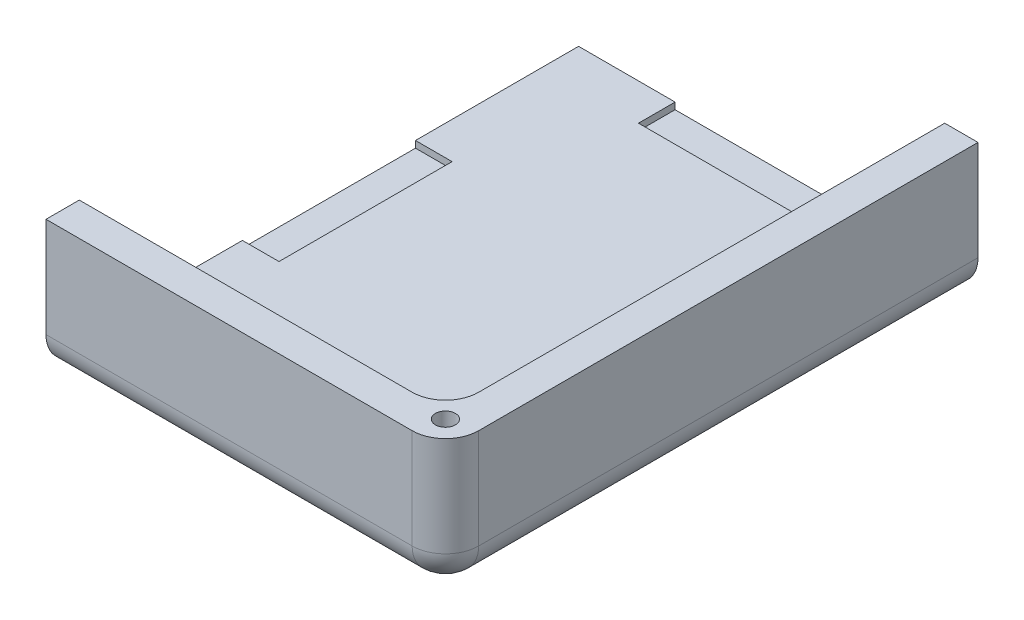
SolidWorks part; units mm, degrees
ref_plane "Plan de face" through (0, 0, 0) normal (0, 0, 1) x (1, 0, 0)
ref_plane "Plan de dessus" through (0, 0, 0) normal (0, 1, 0) x (1, 0, 0)
ref_plane "Plan de droite" through (0, 0, 0) normal (1, 0, 0) x (0, 0, -1)
sketch "Esquisse1" plane through (0, 0, 0) normal (0, 1, 0) x (1, 0, 0)
  line L1 (0, 0) -> (120, 0)
  line L2 (0, 0) -> (0, 160)
  line L3 (0, 160) -> (120, 160)
  line L4 (120, 0) -> (120, 160)
  dimension "D1" = 160
  dimension "D2" = 120
extrude "Boss.-Extru.1" add sketch "Esquisse1" along normal blind 40
sketch "Esquisse2" plane through (0, 40, 0) normal (0, 1, 0) x (1, 0, 0)
  line L0 (120, 0) -> (120, 160) construction
  line L1 (0, 160) -> (110, 160)
  line L2 (0, 160) -> (0, 10)
  line L3 (0, 10) -> (110, 10)
  line L4 (110, 160) -> (110, 10)
  line L5 (0, 0) -> (120, 0) construction
  dimension "D1" = 10
  dimension "D2" = 10
extrude "Enlèv. mat.-Extru.1" cut sketch "Esquisse2" against normal blind 35
fillet "Congé1" radius 10 1 edges at (60, 0, 0)
fillet "Congé2" radius 10 3 edges at (120, 25, 0) (120, 2.9289, -2.9289) (120, 0, -85)
fillet "Congé3" radius 10 1 edges at (110, 22.5, -10)
sketch "Esquisse3" plane through (0, 0, 0) normal (0, -1, 0) x (1, 0, 0)
  line L0 (110, -10) -> (0, -10) construction
  line L1 (110, -160) -> (110, -10) construction
  circle A0 centre (90, -30) radius 2.5
  dimension "D3" = 5
  dimension "D1" = 20
  dimension "D2" = 20
extrude "Boss.-Extru.2" add sketch "Esquisse3" along normal blind 2.5
fillet "Congé4" radius 2.5 1 edges at (90, -2.5, -32.5)
sketch "Esquisse4" plane through (0, 40, 0) normal (0, 1, 0) x (1, 0, 0)
  line L0 (120, 10) -> (120, 160) construction
  line L1 (0, 0) -> (110, 0) construction
  circle A0 centre (112, 8) radius 3
  dimension "D3" = 6
  dimension "D1" = 8
  dimension "D2" = 8
extrude "Enlèv. mat.-Extru.2" cut sketch "Esquisse4" against normal blind 35
sketch "Esquisse5" plane through (0, 5, 0) normal (0, 1, 0) x (1, 0, 0)
  line L0 (0, 160) -> (0, 10) construction
  line L1 (0, 59) -> (11, 59)
  line L2 (0, 59) -> (0, 111)
  line L3 (0, 111) -> (11, 111)
  line L4 (11, 59) -> (11, 111)
  line L5 (110, 160) -> (0, 160) construction
  line L6 (29, 160) -> (81, 160)
  line L7 (29, 160) -> (29, 149)
  line L8 (29, 149) -> (81, 149)
  line L9 (81, 160) -> (81, 149)
  line L10 (0, 10) -> (100, 10) construction
  line L11 (110, 20) -> (110, 160) construction
  dimension "D1" = 49
  dimension "D2" = 49
  dimension "D3" = 11
  dimension "D4" = 29
  dimension "D5" = 29
  dimension "D6" = 11
extrude "Enlèv. mat.-Extru.3" cut sketch "Esquisse5" against normal blind 2
sketch "Esquisse6" plane through (0, 0, -10) normal (0, 0, -1) x (-1, 0, 0)
  line L0 (0, 5) -> (0, 40) construction
  line L1 (0, 33.5) -> (-26, 33.5)
  line L2 (0, 33.5) -> (0, 11.5)
  line L3 (0, 11.5) -> (-26, 11.5)
  line L4 (-26, 33.5) -> (-26, 11.5)
  line L5 (0, 5) -> (-100, 5) construction
  line L6 (0, 40) -> (-100, 40) construction
  dimension "D1" = 6.5
  dimension "D2" = 6.5
  dimension "D3" = 26
extrude "Enlèv. mat.-Extru.4" cut sketch "Esquisse6" against normal blind 2
sketch "Esquisse7" plane through (110, 0, 0) normal (-1, 0, 0) x (0, 0, 1)
  line L0 (-160, 5) -> (-160, 40) construction
  line L1 (-160, 11.5) -> (-134, 11.5)
  line L2 (-160, 11.5) -> (-160, 33.5)
  line L3 (-160, 33.5) -> (-134, 33.5)
  line L4 (-134, 11.5) -> (-134, 33.5)
  line L5 (-20, 5) -> (-160, 5) construction
  line L6 (-20, 40) -> (-160, 40) construction
  dimension "D1" = 6.5
  dimension "D2" = 6.5
  dimension "D3" = 26
extrude "Enlèv. mat.-Extru.5" cut sketch "Esquisse7" against normal blind 2
